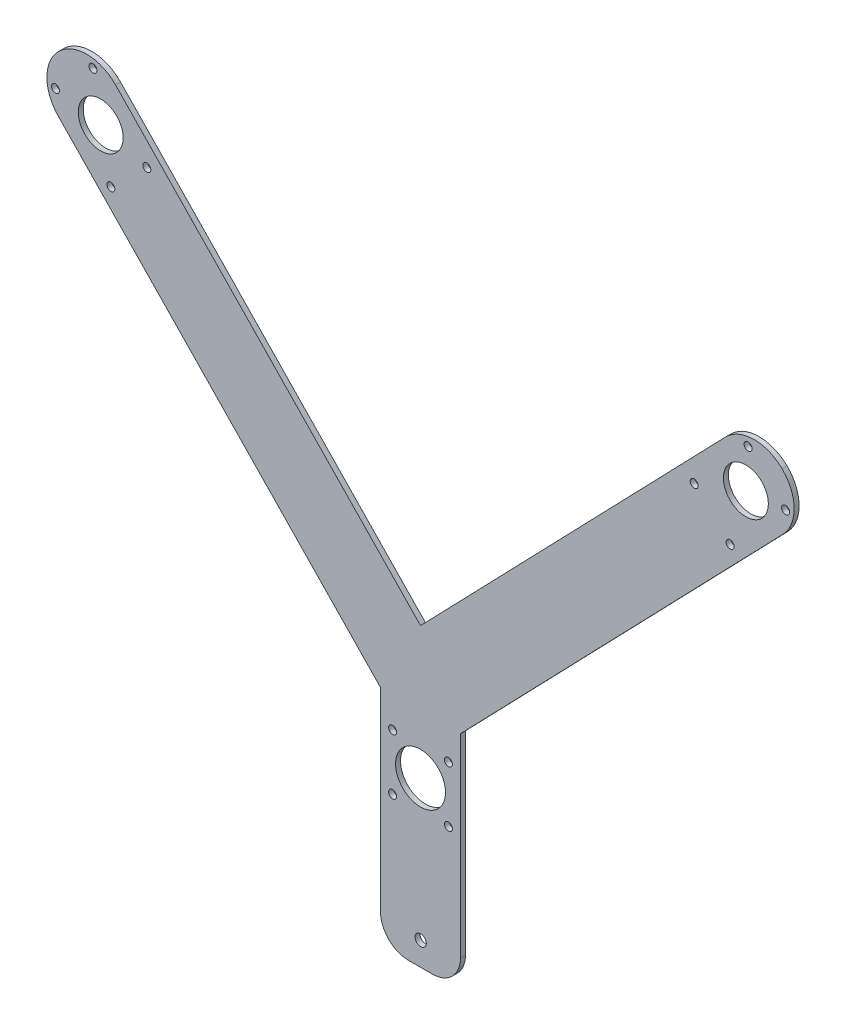
SolidWorks part; units mm, degrees
ref_plane "Front Plane" through (0, 0, 0) normal (0, 0, 1) x (1, 0, 0)
ref_plane "Top Plane" through (0, 0, 0) normal (0, 1, 0) x (1, 0, 0)
ref_plane "Right Plane" through (0, 0, 0) normal (1, 0, 0) x (0, 0, -1)
sketch "Sketch1" plane through (0, 0, 0) normal (0, 0, 1) x (1, 0, 0)
  line L0 (0, 0) -> (50.8, 0)
  line L1 (50.8, 0) -> (50.8, 141.3009)
  line L2 (50.8, 141.3009) -> (273.4748, 371.8874)
  line L3 (0, 0) -> (0, 141.3009)
  line L4 (0, 141.3009) -> (-222.6748, 371.8874)
  line L5 (-222.6748, 371.8874) -> (-186.1323, 407.1761)
  line L6 (-186.1323, 407.1761) -> (25.4, 188.1279)
  line L7 (25.4, 188.1279) -> (236.9323, 407.1761)
  line L8 (236.9323, 407.1761) -> (273.4748, 371.8874)
  circle A0 centre (25.4, 800.087) radius 406.4 construction
  point P3 (-80.3662, 297.652)
  dimension "D1" = 812.8
  dimension "D3" = 50.8
  dimension "D4" = 50.8
  dimension "D5" = 50.8
  dimension "D6" = 88
extrude "Boss-Extrude1" add sketch "Sketch1" along normal blind 3.175 contours L1 L2 L8 L7 L6 L5 L4 L3 L0
sketch "Sketch2" plane through (0, 0, 3.175) normal (0, 0, 1) x (1, 0, 0)
  line L0 (50.8, 141.3009) -> (273.4748, 371.8874) construction
  line L1 (-186.1323, 407.1761) -> (25.4, 188.1279) construction
  line L2 (236.9323, 407.1761) -> (273.4748, 371.8874) construction
  line L3 (-222.6748, 371.8874) -> (-186.1323, 407.1761) construction
  line L4 (50.8, 0) -> (50.8, 141.3009) construction
  line L5 (0, 0) -> (50.8, 0) construction
  line L11 (43.1292, 121.8692) -> (7.6708, 86.4108) construction
  line L12 (43.1292, 86.4108) -> (7.6708, 121.8692) construction
  circle A0 centre (232.2659, 365.7791) radius 14.2875
  circle A1 centre (-177.9371, 362.1249) radius 14.2875
  circle A2 centre (25.4, 104.14) radius 15.875
  circle A3 centre (43.1292, 121.8692) radius 2.54
  circle A4 centre (7.6708, 121.8692) radius 2.54
  circle A5 centre (7.6708, 86.4108) radius 2.54
  circle A6 centre (43.1292, 86.4108) radius 2.54
  point P26 (0, 0)
  point P27 (0, 0)
  dimension "D2" = 28.575
  dimension "D3" = 25.4
  dimension "D4" = 28.575
  dimension "D5" = 33.02
  dimension "D6" = 38.1
  dimension "D8" = 31.75
  dimension "D9" = 104.14
  dimension "D12" = 5.08
  dimension "D13" = 5.08
  dimension "D14" = 5.08
  dimension "D1" = 25.4
  dimension "D7" = 25.4
  dimension "D10" = 35.4584
  dimension "D11" = 35.4584
extrude "Cut-Extrude1" cut sketch "Sketch2" against normal through all
fillet "Fillet1" radius 25.4 4 edges at (273.4748, 371.8874, 1.5875) (236.9323, 407.1761, 1.5875) (-222.6748, 371.8874, 1.5875) (-186.1323, 407.1761, 1.5875)
sketch "Sketch7" plane through (0, 0, 0) normal (0, 0, -1) x (-1, 0, 0)
  circle A0 centre (-25.5077, 14.9496) radius 3.556
  dimension "D1" = 7.112
extrude "Cut-Extrude6" cut sketch "Sketch7" against normal through all contours A0
fillet "Fillet2" radius 17.78 1 edges at (0, 0, 1.5875)
fillet "Fillet3" radius 17.78 1 edges at (50.8, 0, 1.5875)
sketch "Sketch9" plane through (0, 0, 0) normal (0, 0, -1) x (-1, 0, 0)
  line L0 (-257.5429, 367.8521) -> (-222.2543, 331.3096) construction
  line L1 (-222.2543, 331.3096) -> (-199.4152, 353.365) construction
  line L2 (-199.4152, 353.365) -> (-233.6982, 390.8786) construction
  line L3 (-233.6982, 390.8786) -> (-257.5429, 367.8521) construction
  line L4 (-50.8, 141.3009) -> (-255.8305, 353.6162) construction
  circle A2 centre (-233.6982, 390.8786) radius 2.54
  circle A3 centre (-257.5429, 367.8521) radius 2.54
  circle A4 centre (-199.4152, 353.365) radius 2.54
  circle A5 centre (-222.2543, 331.3096) radius 2.54
  dimension "D2" = 50.8
  dimension "D4" = 31.75
  dimension "D1" = 31.75
  dimension "D3" = 15.875
extrude "Cut-Extrude7" cut sketch "Sketch9" against normal through all
ref_plane "Plane3" through (25.4, 0, 0) normal (-1, 0, 0) x (0, 0, 1)
mirror "Mirror3" about plane through (25.4, 0, 0) normal (-1, 0, 0) of "Cut-Extrude7"
